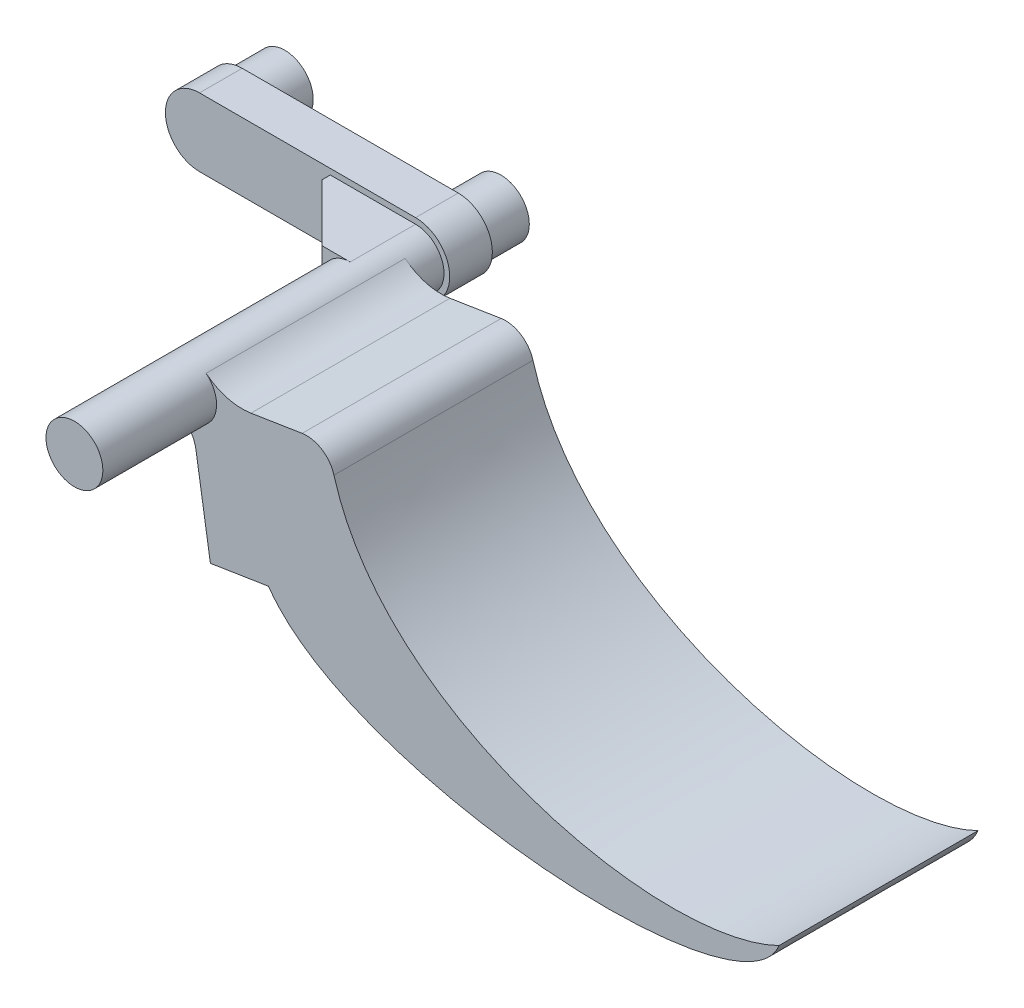
SolidWorks part; units mm, degrees
ref_plane "Спереди" through (0, 0, 0) normal (0, 0, 1) x (1, 0, 0)
ref_plane "Сверху" through (0, 0, 0) normal (0, 1, 0) x (1, 0, 0)
ref_plane "Справа" through (0, 0, 0) normal (1, 0, 0) x (0, 0, -1)
sketch "Эскиз1" plane through (0, 0, 0) normal (0, 0, 1) x (1, 0, 0)
  circle A0 centre (0, 0) radius 1
  dimension "D1" = 2
extrude "Бобышка-Вытянуть1" add sketch "Эскиз1" along normal blind 15
ref_plane "Плоскость1" through (0, 0, 1.5) normal (0, 0, -1) x (-1, 0, 0)
sketch "Эскиз2" plane through (0, 0, 1.5) normal (0, 0, -1) x (-1, 0, 0)
  line L0 (0, 1.201) -> (7.6, 1.201)
  line L1 (0, -1.199) -> (7.6, -1.199)
  arc A0 (7.6, -1.199) -> (7.6, 1.201) centre (7.6, 0.001) ccw
  arc A1 (0, 1.201) -> (0, -1.199) centre (0, 0.001) ccw
  point P6 (-1.2, 0.001)
  point P7 (8.8, 0.001)
  dimension "D2" = 2.4
  dimension "D3" = 10
extrude "Бобышка-Вытянуть2" add sketch "Эскиз2" against normal blind 1.5
sketch "Эскиз3" plane through (0, 0, 3) normal (0, 0, 1) x (1, 0, 0)
  circle A0 centre (-7.6, 0.001) radius 1
  dimension "D1" = 2
extrude "Бобышка-Вытянуть3" add sketch "Эскиз3" against normal blind 3
sketch "Эскиз4" plane through (0, 0, 3) normal (0, 0, 1) x (1, 0, 0)
  line L1 (0, 1) -> (-3, 1)
  line L2 (0, 1) -> (0, -1)
  line L3 (0, -1) -> (-3, -1)
  line L4 (-3, 1) -> (-3, -1)
  circle A0 centre (0, 0) radius 1 construction
  point P6 (-3, 0)
  dimension "D1" = 2
  dimension "D2" = 3
extrude "Бобышка-Вытянуть4" add sketch "Эскиз4" along normal blind 2.3
ref_plane "Плоскость2" through (0, 0, 4) normal (0, 0, -1) x (-1, 0, 0)
sketch "Эскиз5" plane through (0, 0, 4) normal (0, 0, -1) x (-1, 0, 0)
  line L0 (0, 0) -> (-0.7822, -4.9384)
  line L1 (0, 0) -> (-4.9384, 0.7822)
  line L2 (-0.7822, -4.9384) -> (-5.7206, -4.1563)
  line L3 (-4.9384, 0.7822) -> (-5.7206, -4.1563)
  line L4 (0, -1.199) -> (7.6, -1.199) construction
  dimension "D1" = 5
  dimension "D2" = 5
  dimension "D3" = 99
extrude "Бобышка-Вытянуть5" add sketch "Эскиз5" against normal blind 7
sketch "Эскиз6" plane through (0, 0, 4) normal (0, 0, -1) x (-1, 0, 0)
  line L0 (-4.9384, 0.7822) -> (-5.7206, -4.1563) construction
  line L1 (-5.7206, -4.1563) -> (-0.7822, -4.9384) construction
  line L7 (-0.9877, 0.1564) -> (-4.9384, 0.7822)
  line L8 (-4.9384, 0.7822) -> (-5.7206, -4.1563)
  line L9 (-5.7206, -4.1563) -> (-0.7822, -4.9384)
  line L10 (-0.7822, -4.9384) -> (-0.1564, -0.9877)
  line L11 (-0.9877, 0.1564) -> (-4.9384, 0.7822)
  line L13 (-2.8266, -4.6146) -> (-0.7822, -4.9384)
  line L14 (-0.7822, -4.9384) -> (-0.1564, -0.9877)
  arc A1 (-0.9877, 0.1564) -> (-0.1564, -0.9877) centre (0, 0) ccw
  arc A2 (-0.9877, 0.1564) -> (-0.1564, -0.9877) centre (0, 0) ccw
  spline S0 degree 3 poles (-4.9384, 0.7822) (-6.0359, -6.1471) (-16.4473, -8.7079) (-20.7822, -6.5825) knots 0 0 0 0 1 1 1 1
  spline S1 degree 3 poles (-20.7822, -6.5825) (-19.5026, -9.7613) (-5.6774, -8.7874) (-2.8266, -4.6146) knots 0 0 0 0 1 1 1 1
  point P8 (-20.7822, -6.151)
  point P13 (-3.7114, -7.4961)
  point P14 (-3.7368, -7.9275)
  point P15 (-20.7822, -6.5825)
  dimension "D2" = 0
  dimension "D1" = 20
extrude "Бобышка-Вытянуть6" add sketch "Эскиз6" against normal blind 7
fillet "Скругление1" radius 1 1 edges at (4.9384, 0.7822, 7.5)
fillet "Скругление2" radius 1 1 edges at (0.1564, -0.9877, 7.5)
fillet "Скругление3" radius 2 1 edges at (0.9877, 0.1564, 7.5)
chamfer "Фаска2" distance 2 angle 45 1 edges at (-3, 0, 5.3)
